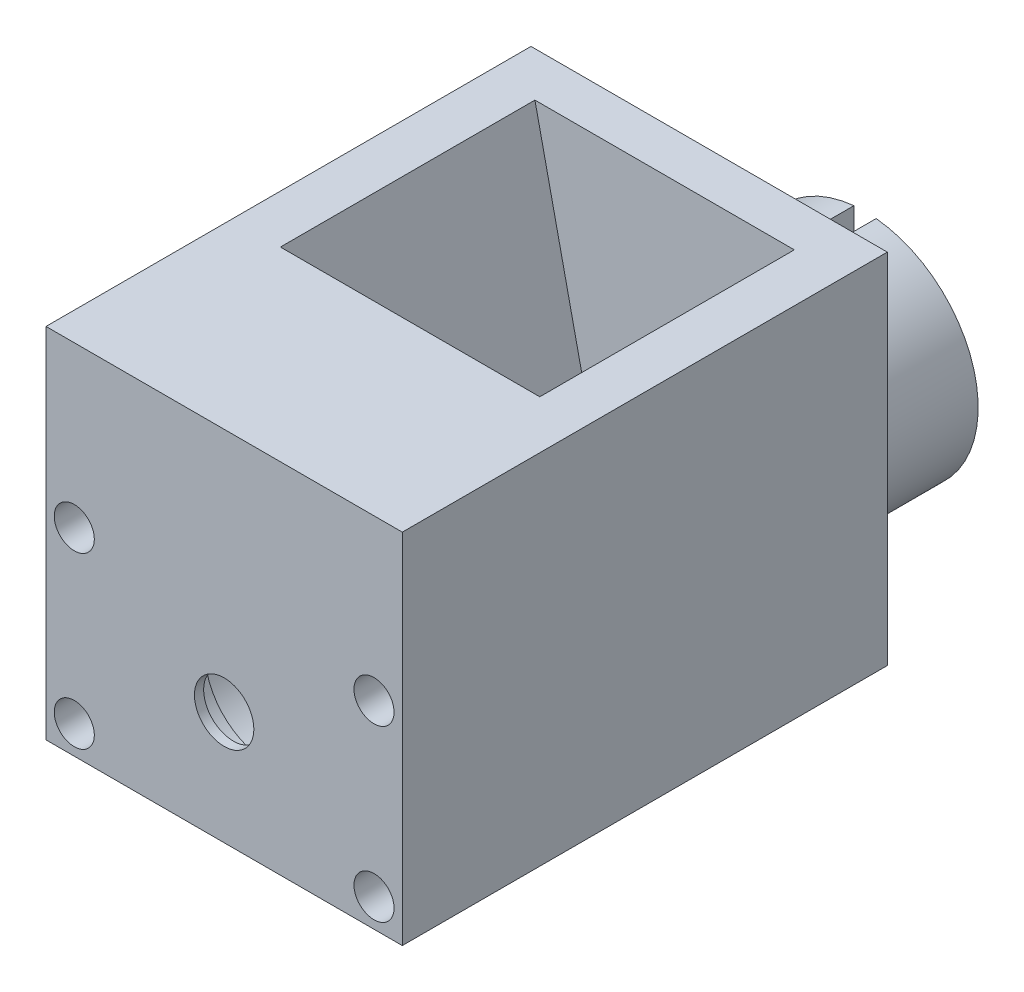
SolidWorks part; units mm, degrees
ref_plane "Front" through (0, 0, 0) normal (0, 0, 1) x (1, 0, 0)
ref_plane "Top" through (0, 0, 0) normal (0, 1, 0) x (1, 0, 0)
ref_plane "Right" through (0, 0, 0) normal (1, 0, 0) x (0, 0, -1)
sketch "Sketch1" plane through (0, 0, 0) normal (0, 0, 1) x (1, 0, 0)
  line L0 (0, 0) -> (0, 55) construction
  line L1 (24.8074, -5.4546) -> (38.1, 55)
  line L2 (38.1, 55) -> (-38.1, 55)
  line L3 (-24.8074, -5.4546) -> (-38.1, 55)
  circle A0 centre (0, 0) radius 16.129
  arc A1 (-24.8074, -5.4546) -> (24.8074, -5.4546) centre (0, 0) ccw
  dimension "D1" = 32.258
  dimension "D2" = 50.8
  dimension "D3" = 55
  dimension "D4" = 38.1
extrude "Boss-Extrude1" add sketch "Sketch1" along normal blind 10
sketch "Sketch2" plane through (0, 0, 10) normal (0, 0, 1) x (1, 0, 0)
  line L0 (-29.1195, 55) -> (-38.1, 55)
  line L3 (16.241, -3.571) -> (29.1195, 55)
  line L4 (38.1, 55) -> (-38.1, 55) construction
  line L5 (-16.241, -3.571) -> (-29.1195, 55)
  line L9 (-38.1, 55) -> (-24.8074, -5.4546)
  line L10 (24.8074, -5.4546) -> (38.1, 55)
  line L11 (38.1, 55) -> (-38.1, 55)
  line L12 (-38.1, 55) -> (-24.8074, -5.4546)
  line L13 (24.8074, -5.4546) -> (38.1, 55)
  line L14 (38.1, 55) -> (29.1195, 55)
  circle A4 centre (0, 0) radius 16.629
  arc A5 (-16.241, -3.571) -> (16.241, -3.571) centre (0, 0) ccw
  arc A6 (-24.8074, -5.4546) -> (24.8074, -5.4546) centre (0, 0) ccw
  arc A7 (-24.8074, -5.4546) -> (24.8074, -5.4546) centre (0, 0) ccw
  dimension "D1" = 0.5
  dimension "D2" = 0
extrude "Boss-Extrude2" add sketch "Sketch2" along normal blind 88.9
sketch "Sketch3" plane through (0, 0, 98.9) normal (0, 0, 1) x (1, 0, 0)
  line L0 (29.1195, 55) -> (-29.1195, 55)
  line L6 (-16.241, -3.571) -> (-29.1195, 55)
  line L7 (-29.1195, 55) -> (-38.1, 55)
  line L8 (-38.1, 55) -> (-24.8074, -5.4546)
  line L9 (24.8074, -5.4546) -> (38.1, 55)
  line L10 (38.1, 55) -> (29.1195, 55)
  line L11 (29.1195, 55) -> (16.241, -3.571)
  line L13 (-29.1195, 55) -> (-38.1, 55)
  line L14 (-38.1, 55) -> (-24.8074, -5.4546)
  line L15 (24.8074, -5.4546) -> (38.1, 55)
  line L16 (38.1, 55) -> (29.1195, 55)
  arc A2 (-16.241, -3.571) -> (16.241, -3.571) centre (0, 0) ccw
  arc A3 (-24.8074, -5.4546) -> (24.8074, -5.4546) centre (0, 0) ccw
  arc A5 (-24.8074, -5.4546) -> (24.8074, -5.4546) centre (0, 0) ccw
  dimension "D1" = 0
extrude "Boss-Extrude3" add sketch "Sketch3" along normal blind 10
sketch "Sketch4" plane through (0, 0, 0) normal (0, 0, -1) x (-1, 0, 0)
  circle A0 centre (0, 0) radius 19.05
  circle A1 centre (0, 0) radius 25.4
  dimension "D1" = 38.1
extrude "Boss-Extrude4" add sketch "Sketch4" along normal blind 35
sketch "Sketch5" plane through (0, 0, -35) normal (0, 0, -1) x (-1, 0, 0)
  line L0 (0, 25.4) -> (0, -25.4) construction
  line L1 (-2.5, 25.4) -> (-2.5, -25.4)
  line L2 (2.5, 25.4) -> (2.5, -25.4)
  line L3 (2.5, 25.4) -> (-2.5, 25.4)
  line L4 (2.5, -25.4) -> (-2.5, -25.4)
  circle A0 centre (0, 0) radius 25.4 construction
  dimension "D1" = 2.5
  dimension "D2" = 2.5
extrude "Cut-Extrude1" cut sketch "Sketch5" against normal blind 20
sketch "Sketch6" plane through (0, 0, 98.9) normal (0, 0, -1) x (-1, 0, 0)
  circle A0 centre (0, 0) radius 16.129 construction
  circle A1 centre (0, 0) radius 16.129 construction
  circle A2 centre (0, -0.6177) radius 14.3129
  dimension "D1" = 28.6258
extrude "Cut-Extrude2" cut sketch "Sketch6" against normal blind 7.9375
sketch "Sketch7" plane through (0, 0, 106.8375) normal (0, 0, -1) x (-1, 0, 0)
  circle A0 centre (0, 0) radius 6.6675
  dimension "D1" = 13.335
extrude "Cut-Extrude3" cut sketch "Sketch7" against normal up to next
sketch "Sketch8" plane through (0, 0, 108.9) normal (0, 0, 1) x (1, 0, 0)
  line L0 (-40, -25.4) -> (40, -25.4)
  line L1 (40, -25.4) -> (40, 24.6)
  line L3 (24.8074, -5.4546) -> (38.1, 55) construction
  line L4 (0, -25.4) -> (0, 55) construction
  line L5 (38.1, 55) -> (-38.1, 55) construction
  line L6 (-24.8074, -5.4546) -> (-31.7176, 25.9729)
  line L8 (-40, -25.4) -> (-40, 24.6)
  line L9 (38.1, 55) -> (-38.1, 55)
  line L10 (-38.1, 55) -> (-24.8074, -5.4546)
  line L11 (24.8074, -5.4546) -> (38.1, 55)
  line L14 (24.8074, -5.4546) -> (31.7176, 25.9729)
  line L15 (40, 24.6) -> (40, 55)
  line L16 (38.1, 55) -> (31.7176, 25.9729)
  line L17 (-40, 24.6) -> (-40, 55)
  line L19 (-38.1, 55) -> (-31.7176, 25.9729)
  line L20 (38.1, 55) -> (40, 55)
  line L21 (-38.1, 55) -> (-40, 55)
  circle A1 centre (0, 0) radius 6.6675 construction
  arc A3 (-24.8074, -5.4546) -> (24.8074, -5.4546) centre (0, 0) ccw
  arc A4 (-24.8074, -5.4546) -> (24.8074, -5.4546) centre (0, 0) ccw
  point P2 (0, -25.4)
  dimension "D1" = 40
  dimension "D4" = 0
  dimension "D2" = 0
extrude "Boss-Extrude5" add sketch "Sketch8" against normal up to surface (108.9 mm away) up to face at (0, 32.4864, 0)
fillet "Fillet1" radius 10 1 edges at (-25.4, 0, 0)
sketch "Sketch9" plane through (0, 0, 108.9) normal (0, 0, 1) x (1, 0, 0)
  circle A0 centre (33.65, 19.05) radius 4.5
  circle A1 centre (-33.65, 19.05) radius 4.5
  circle A2 centre (-33.65, -19.05) radius 4.5
  circle A3 centre (33.65, -19.05) radius 4.5
  dimension "D1" = 9
extrude "Cut-Extrude4" cut sketch "Sketch9" against normal blind 10
sketch "Sketch11" plane through (0, 0, 98.9) normal (0, 0, -1) x (-1, 0, 0)
  line L3 (16.241, -3.571) -> (29.1195, 55)
  line L4 (29.1195, 55) -> (-29.1195, 55)
  line L5 (-29.1195, 55) -> (-16.241, -3.571)
  line L6 (16.241, -3.571) -> (29.1195, 55)
  line L7 (29.1195, 55) -> (-29.1195, 55)
  line L8 (-29.1195, 55) -> (-16.241, -3.571)
  arc A0 (16.241, -3.571) -> (-16.241, -3.571) centre (0, 0) ccw
  arc A2 (-16.241, -3.571) -> (16.241, -3.571) centre (0, 0) ccw
  dimension "D1" = 0
extrude "Boss-Extrude6" add sketch "Sketch11" along normal offset from surface (31.75 mm away) 57.15 up to face at (0, 22.45, 10)
